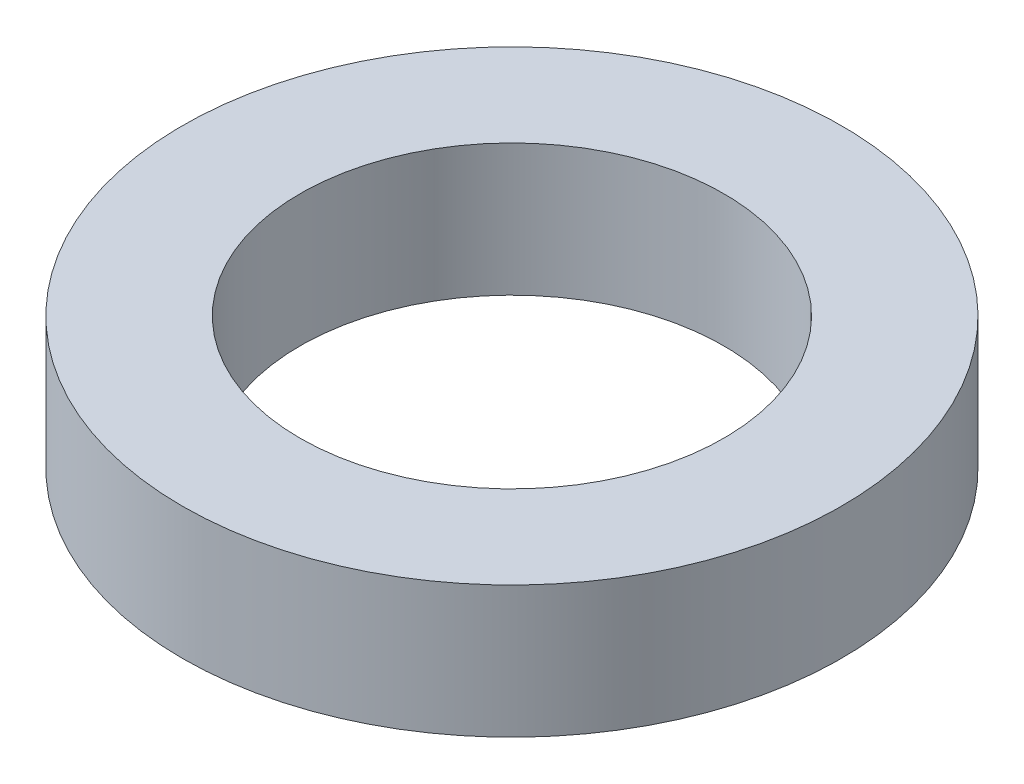
SolidWorks part; units mm, degrees
ref_plane "Front Plane" through (0, 0, 0) normal (0, 0, 1) x (1, 0, 0)
ref_plane "Top Plane" through (0, 0, 0) normal (0, 1, 0) x (1, 0, 0)
ref_plane "Right Plane" through (0, 0, 0) normal (1, 0, 0) x (0, 0, -1)
sketch "Sketch1" plane through (0, 0, 0) normal (0, 1, 0) x (1, 0, 0)
  circle A0 centre (0, 0) radius 35
  dimension "FLANGE_OD" = 70
extrude "Boss-Extrude1" add sketch "Sketch1" along normal blind 14
sketch "Sketch2" plane through (0, 0, 0) normal (0, 1, 0) x (1, 0, 0)
  circle A0 centre (0, 0) radius 22.5
  dimension "BORE_D" = 45
extrude "Cut-Extrude1" cut sketch "Sketch2" along normal through all
sketch "Sketch3" plane through (0, 14, 0) normal (0, 1, 0) x (1, 0, 0)
  circle A0 centre (0, 0) radius 13.9605 construction
  circle A1 centre (-13.9605, 0) radius 1.7486
  dimension "BOLT_D" = 3.4972
  dimension "BOLT_PCD" = 27.921
extrude "Cut-Extrude2" cut sketch "Sketch3" against normal blind 12.1154 rebuild error yes
pattern_circular "CirPattern1" count 4 over 360 rebuild error yes
